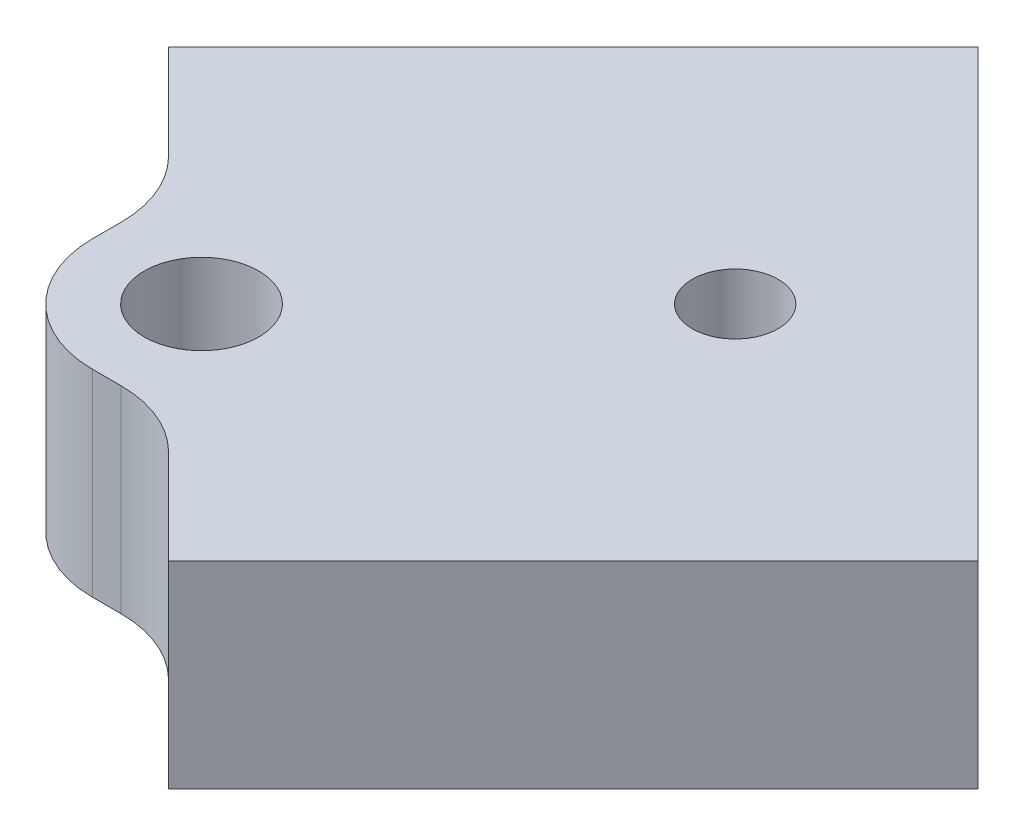
SolidWorks part; units mm, degrees
ref_plane "Ebene vorne" through (0, 0, 0) normal (0, 0, 1) x (1, 0, 0)
ref_plane "Ebene oben" through (0, 0, 0) normal (0, 1, 0) x (1, 0, 0)
ref_plane "Ebene rechts" through (0, 0, 0) normal (1, 0, 0) x (0, 0, -1)
sketch "Skizze1" plane through (0, 0, 0) normal (0, 1, 0) x (1, 0, 0)
  line L1 (0, -3.95) -> (1, -3.95)
  line L3 (0, 0) -> (50000, 0) construction
  line L4 (0, 0) -> (35355.3391, 35355.3391) construction
  line L8 (-3.95, 0) -> (-3.95, 1)
  line L10 (-8.4247, 7.1316) -> (-5.1216, 3.8284)
  line L11 (-8.4247, 7.1316) -> (5.7174, 21.2737)
  line L12 (3.8284, -5.1216) -> (7.1316, -8.4247)
  line L13 (5.7174, 21.2737) -> (21.2737, 5.7174)
  line L14 (21.2737, 5.7174) -> (7.1316, -8.4247)
  arc A0 (-3.95, 0) -> (0, -3.95) centre (0, 0) ccw
  arc A1 (3.8284, -5.1216) -> (1, -3.95) centre (1, -7.95) ccw
  arc A2 (-3.95, 1) -> (-5.1216, 3.8284) centre (-7.95, 1) ccw
  dimension "D2" = 7.9
  dimension "D7" = 8
  dimension "D1" = 1
  dimension "D3" = 22
  dimension "D4" = 45
  dimension "D5" = 20
  dimension "D8" = 1
extrude "Aufsatz-Linear austragen1" add sketch "Skizze1" along normal blind 6.9
hole_wizard "Ø4.0 (4) Durchmesser Bohrung1" positions "Skizze2" profile "Skizze3" hole size "Ø4.0" standard "ISO" end condition through all
sketch "Skizze2" plane through (0, 6.9, 0) normal (0, 1, 0) x (1, 0, 0)
  line L1 (0, 0) -> (-50000, 0) construction
  line L2 (0, 0) -> (-35355.3391, -35355.3391) construction
  point P9 (-0.0707, -0.0707)
  dimension "D1" = 45
  dimension "D2" = 0.1
sketch "Skizze3" plane through (-0.0707, 6.9, 0.0707) normal (1, 0, 0) x (0, 0, 1)
  line L0 (0, 0) -> (0, 6.9)
  line L1 (0, 6.9) -> (2, 6.9)
  line L2 (2, 6.9) -> (2, 0)
  line L5 (2, 0) -> (0, 0)
  line L11 (0, -6.35) -> (0, 107.95) construction
  dimension "Bohrerdurchmesser" = 4
  dimension "Bohrungstiefe" = 6.9
hole_wizard "Ø3.0 (3) Durchmesser Bohrung1" positions "Skizze4" profile "Skizze5" hole size "Ø3.0" standard "ISO" end condition through all
sketch "Skizze4" plane through (0, 6.9, 0) normal (0, 1, 0) x (1, 0, 0)
  line L0 (0, 0) -> (-50000, 0) construction
  line L1 (0, 0) -> (35355.3391, 35355.3391) construction
  line L2 (21.2737, 5.7174) -> (5.7174, 21.2737) construction
  point P7 (9.2529, 9.2529)
  dimension "D1" = 45
  dimension "D2" = 6
sketch "Skizze5" plane through (9.2529, 6.9, -9.2529) normal (1, 0, 0) x (0, 0, 1)
  line L0 (0, 0) -> (0, 6.9)
  line L1 (0, 6.9) -> (1.5, 6.9)
  line L2 (1.5, 6.9) -> (1.5, 0)
  line L5 (1.5, 0) -> (0, 0)
  line L11 (0, -6.35) -> (0, 107.95) construction
  dimension "Bohrerdurchmesser" = 3
  dimension "Bohrungstiefe" = 6.9
